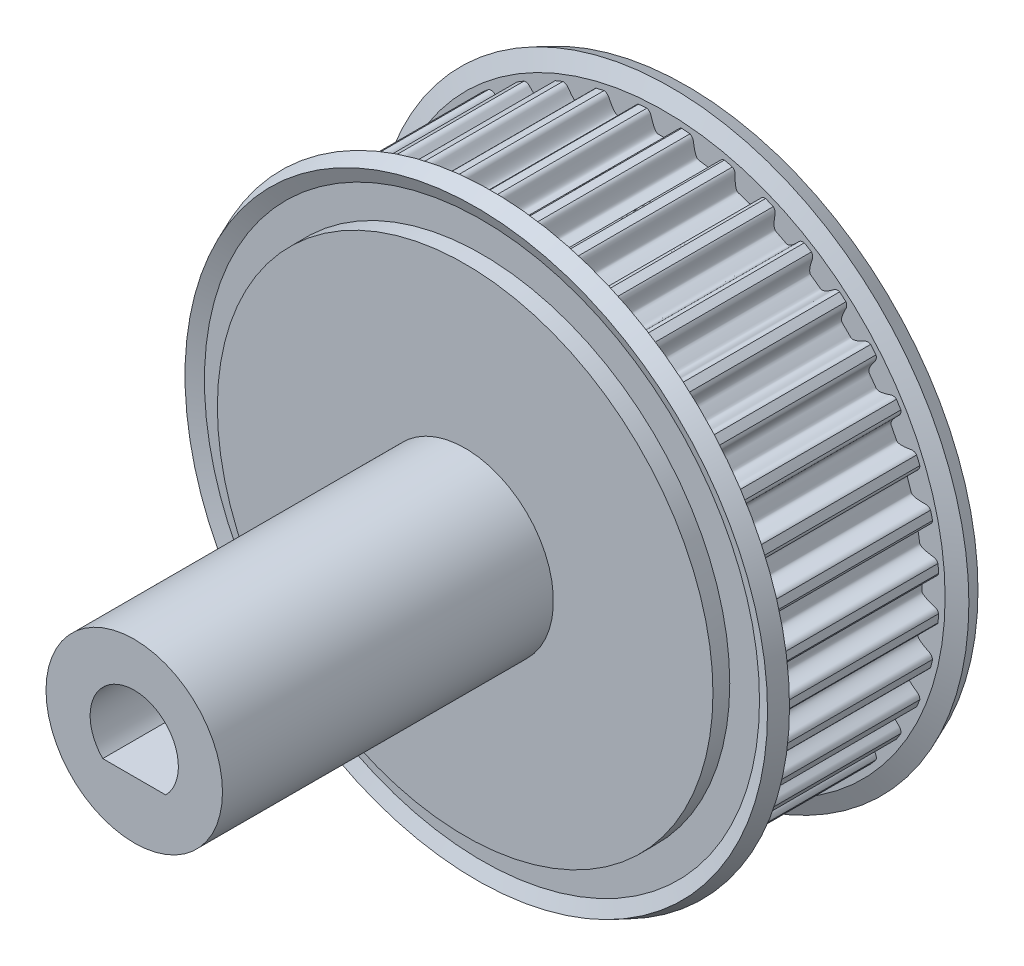
SolidWorks part; units mm, degrees
ref_plane "前视基准面" through (0, 0, 0) normal (0, 0, 1) x (1, 0, 0)
ref_plane "上视基准面" through (0, 0, 0) normal (0, 1, 0) x (1, 0, 0)
ref_plane "右视基准面" through (0, 0, 0) normal (1, 0, 0) x (0, 0, -1)
other "Configuration Table"
ref_axis "基准轴1" through (0, 0, 55) along (0, 0, -1)
sketch "SketchRevolveGearBelt01" plane through (0, 0, 0) normal (1, 0, 0) x (0, 0, -1)
  line L0 (0, 0) -> (1, 0) construction
  line L1 (5.274, 0) -> (5.274, 11.2324)
  line L2 (5.274, 11.2324) -> (4.512, 11.2324)
  line L3 (4.512, 11.2324) -> (4.512, 12.5808)
  line L4 (4.512, 12.5808) -> (4.7696, 13.2028)
  line L5 (4.7696, 13.2028) -> (4.0656, 13.4944)
  line L6 (4.0656, 13.4944) -> (3.75, 12.7324)
  line L7 (3.75, 12.7324) -> (3.75, 12.4636)
  line L8 (3.75, 12.4636) -> (-3.75, 12.4636)
  line L9 (-3.75, 12.4636) -> (-3.75, 12.7324)
  line L10 (-3.75, 12.7324) -> (-4.0656, 13.4944)
  line L11 (-4.0656, 13.4944) -> (-4.7696, 13.2028)
  line L12 (-4.7696, 13.2028) -> (-4.512, 12.5808)
  line L13 (-4.512, 12.5808) -> (-4.512, 11.2324)
  line L14 (-4.512, 11.2324) -> (-5.274, 11.2324)
  line L15 (-5.274, 11.2324) -> (-5.274, 0)
  line L16 (-5.274, 0) -> (5.274, 0)
  dimension "GearBeltFlange1OutsideLength" = 1.3484
  dimension "GearBeltFlange1X" = 0.2576
  dimension "GearBeltFlange1Y" = 0.622
  dimension "GearBeltFlangeThickness" = 0.762
  dimension "GearBeltFlangeInside" = 0.2688
  dimension "GearBeltOutsideDiameter" = 12.4636
  dimension "GearBeltFlange2X" = 0.2576
revolve "Gates_PowerGrip_GT_2mm, 6mm Belt Width" add sketch "SketchRevolveGearBelt01" angle 360 about L0
sketch "SketchToothGearBelt01" plane through (0, 0, 0) normal (0, 0, 1) x (1, 0, 0)
  arc A0 (12.4481, 0.8617) -> (12.4481, -0.8617) centre (0, 0) cw
  spline S0 degree 3 poles (12.4481, -0.8617) (12.4481, -0.8443) (12.4457, -0.8183) (12.4374, -0.7846) (12.4288, -0.7601) (12.4179, -0.7365) (12.4047, -0.7141) (12.3893, -0.6931) (12.372, -0.6736) (12.3529, -0.656) (12.3322, -0.6402) (12.31, -0.6266) (12.2867, -0.6151) (12.2476, -0.6013) (12.1977, -0.5862) (12.1386, -0.5675) (12.0861, -0.5498) (12.0368, -0.5322) (11.9907, -0.5145) (11.9478, -0.4969) (11.908, -0.4793) (11.8715, -0.4616) (11.838, -0.444) (11.8078, -0.4264) (11.7807, -0.4087) (11.7568, -0.3911) (11.736, -0.3735) (11.7184, -0.3558) (11.7039, -0.3381) (11.6926, -0.3203) (11.6845, -0.3025) (11.6794, -0.2846) (11.6772, -0.2503) (11.6804, -0.2) (11.6806, -0.1333) (11.6813, -0.0667) (11.6815, 0) (11.6813, 0.0667) (11.6806, 0.1333) (11.6804, 0.2) (11.6772, 0.2503) (11.6794, 0.2846) (11.6845, 0.3025) (11.6926, 0.3203) (11.7039, 0.3381) (11.7184, 0.3558) (11.736, 0.3735) (11.7568, 0.3911) (11.7807, 0.4087) (11.8078, 0.4264) (11.838, 0.444) (11.8715, 0.4616) (11.908, 0.4793) (11.9478, 0.4969) (11.9907, 0.5145) (12.0368, 0.5322) (12.0861, 0.5498) (12.1386, 0.5675) (12.1977, 0.5862) (12.2476, 0.6013) (12.2867, 0.6151) (12.31, 0.6266) (12.3322, 0.6402) (12.3529, 0.656) (12.372, 0.6736) (12.3893, 0.6931) (12.4047, 0.7141) (12.4179, 0.7365) (12.4288, 0.7601) (12.4374, 0.7846) (12.4457, 0.8183) (12.4481, 0.8443) (12.4481, 0.8617) knots 0 0 0 0 0.019856 0.029784 0.039712 0.04964 0.059568 0.069496 0.079424 0.089352 0.09928 0.109208 0.119136 0.129064 0.156684 0.178987 0.200135 0.220136 0.238998 0.256731 0.273348 0.288863 0.303293 0.316663 0.328999 0.340339 0.350727 0.360226 0.368913 0.376892 0.384296 0.39129 0.39807 0.423571 0.449047 0.474524 0.5 0.525476 0.550953 0.576429 0.60193 0.60871 0.615704 0.623108 0.631087 0.639774 0.649273 0.659661 0.671001 0.683337 0.696707 0.711137 0.726652 0.743269 0.761002 0.779864 0.799865 0.821013 0.843316 0.870936 0.880864 0.890792 0.90072 0.910648 0.920576 0.930504 0.940432 0.95036 0.960288 0.970216 0.980144 1 1 1 1
extrude "ToothExtrudeCutGearBelt01" cut sketch "SketchToothGearBelt01" against normal blind 3.75 and the other way blind 3.75
pattern_circular "Tooth Pattern, 40" count 40 every 9 about axis through (0, 0, 55) along (0, 0, -1) of "ToothExtrudeCutGearBelt01"
sketch "BoreRevolveSketch" plane through (0, 0, 0) normal (1, 0, 0) x (0, 0, -1)
  line L0 (0, 0) -> (1, 0) construction
  line L1 (-5.274, 0) -> (5.274, 0)
  line L2 (5.274, 0) -> (5.274, 5)
  line L3 (5.274, 5) -> (-5.274, 5)
  line L4 (-5.274, 5) -> (-5.274, 0)
  dimension "TaperSide1" = 5
  dimension "TaperSide2" = 5
revolve "BoreRevolveCut" cut sketch "BoreRevolveSketch" angle 360 about L0
sketch "AuxiliarySketchGearBelt01" plane through (0, 0, 0) normal (0, 0, 1) x (1, 0, 0)
  circle A0 centre (0, 0) radius 12.7324 construction
  dimension "PitchDiameter" = 25.4648
sketch "草图5" plane through (0, 0, 5.274) normal (0, 0, 1) x (1, 0, 0)
  circle A0 centre (0, 0) radius 5
extrude "凸台-拉伸1" add sketch "草图5" against normal blind 10
sketch "草图6" plane through (0, 0, 5.274) normal (0, 0, 1) x (1, 0, 0)
  line L0 (0, 0) -> (0, -1.4)
  line L1 (0, -1.4) -> (-1.4283, -1.4)
  line L2 (-1.4283, -1.4) -> (1.4283, -1.4)
  circle A0 centre (0, 0) radius 2
  circle A1 centre (0, 0) radius 4
  dimension "D1" = 4
  dimension "D3" = 1.4
  dimension "D2" = 2
extrude "凸台-拉伸3" add sketch "草图6" along normal blind 15 contours A1 A0 | L1 A0 L2 region at (0, -1.6434, 5.274) region at (-3.8869, 0, 5.274)
sketch "草图7" plane through (0, 0, 5.274) normal (0, 0, 1) x (1, 0, 0)
  circle A0 centre (0, 0) radius 1.9403
extrude "切除-拉伸3" cut sketch "草图7" against normal through all
sketch "草图8" plane through (0, -1.4, 0) normal (0, 1, 0) x (1, 0, 0)
  line L0 (0, -20.274) -> (0, -16.274)
  line L1 (-4, -20.274) -> (4, -20.274) construction
  line L2 (0, -55) -> (0, 55) construction
  circle A0 centre (0, -16.274) radius 1.5
  line M5 (-1.4283, -5.274) -> (-1.4283, -20.274)
  line M7 (1.4283, -20.274) -> (1.4283, -5.274)
  dimension "D2" = 3
  dimension "D1" = 4
extrude "切除-拉伸4" cut sketch "草图8" against normal through all contours A0 M7 M5 region at (1.3869, -1.4, 16.274)
